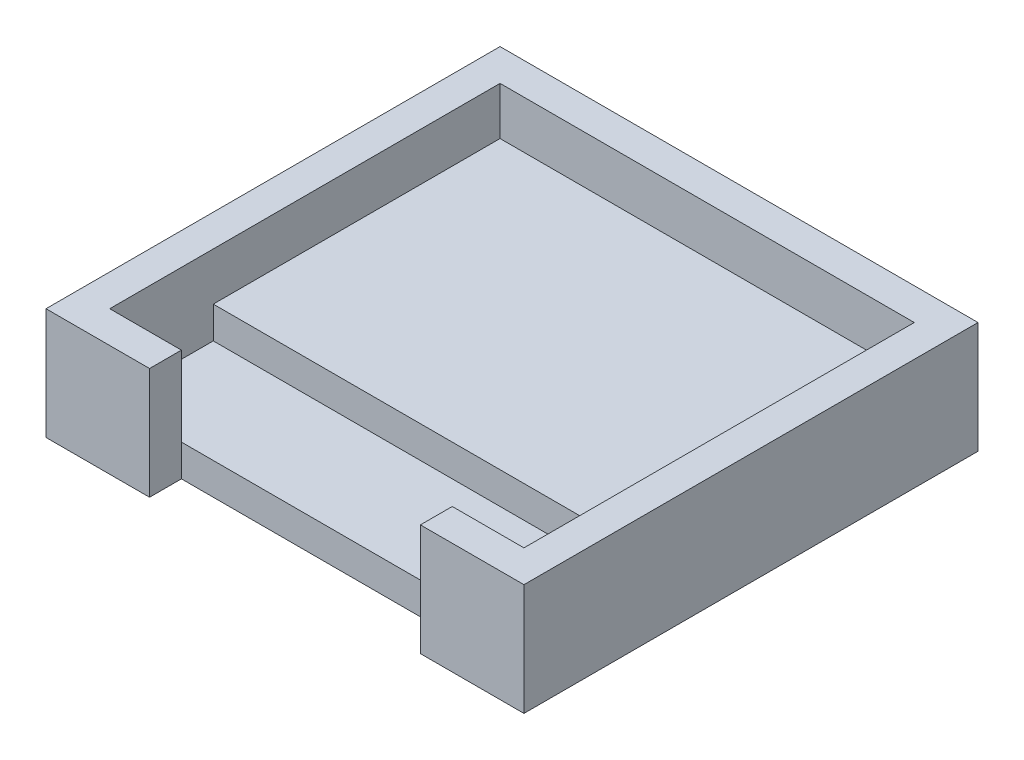
SolidWorks part; units mm, degrees
ref_plane "Front Plane" through (0, 0, 0) normal (0, 0, 1) x (1, 0, 0)
ref_plane "Top Plane" through (0, 0, 0) normal (0, 1, 0) x (1, 0, 0)
ref_plane "Right Plane" through (0, 0, 0) normal (1, 0, 0) x (0, 0, -1)
sketch "Sketch1" plane through (0, 0, 0) normal (0, 1, 0) x (1, 0, 0)
  line L0 (0, 6.5) -> (26, 6.5)
  line L1 (0, 0) -> (26, 0)
  line L2 (0, 0) -> (0, 24.5)
  line L3 (0, 24.5) -> (26, 24.5)
  line L4 (26, 0) -> (26, 24.5)
  line L5 (-2, -2) -> (-2, 26.5)
  line L6 (-2, 26.5) -> (28, 26.5)
  line L7 (28, -2) -> (28, 26.5)
  line L8 (-2, -2) -> (4.5, -2)
  line L9 (21.5, -2) -> (28, -2)
  line L10 (4.5, 0) -> (21.5, 0)
  line L11 (4.5, 0) -> (4.5, -2)
  line L13 (21.5, 0) -> (21.5, -2)
  line L15 (-2, -2) -> (28, -2) construction
  dimension "D1" = 24.5
  dimension "D2" = 26
  dimension "D3" = 6.5
  dimension "D5" = 4.5
  dimension "D6" = 17
  dimension "D4" = 2
extrude "Boss-Extrude1" add sketch "Sketch1" along normal blind 7 contours L1 L13 L9 L7 L6 L5 L8 L11 L2 L3 L4 region at (-0.4138, 0, -3.25)
extrude "Boss-Extrude2" add sketch "Sketch1<3>" along normal blind 2 contours L1 L4 L0 L2 region at (13, 0, -3.25)
sketch "Sketch1<3>" plane through (0, 0, 0) normal (0, 1, 0) x (1, 0, 0) same geometry as "Sketch1"
extrude "Boss-Extrude3" add sketch "Sketch1<5>" along normal blind 4 contours L0 L4 L3 L2 region at (13, 0, -15.5)
sketch "Sketch1<5>" plane through (0, 0, 0) normal (0, 1, 0) x (1, 0, 0) same geometry as "Sketch1"
equation "\"D5@Sketch1\"=(\"D2@Sketch1\"-\"D6@Sketch1\")/2"
